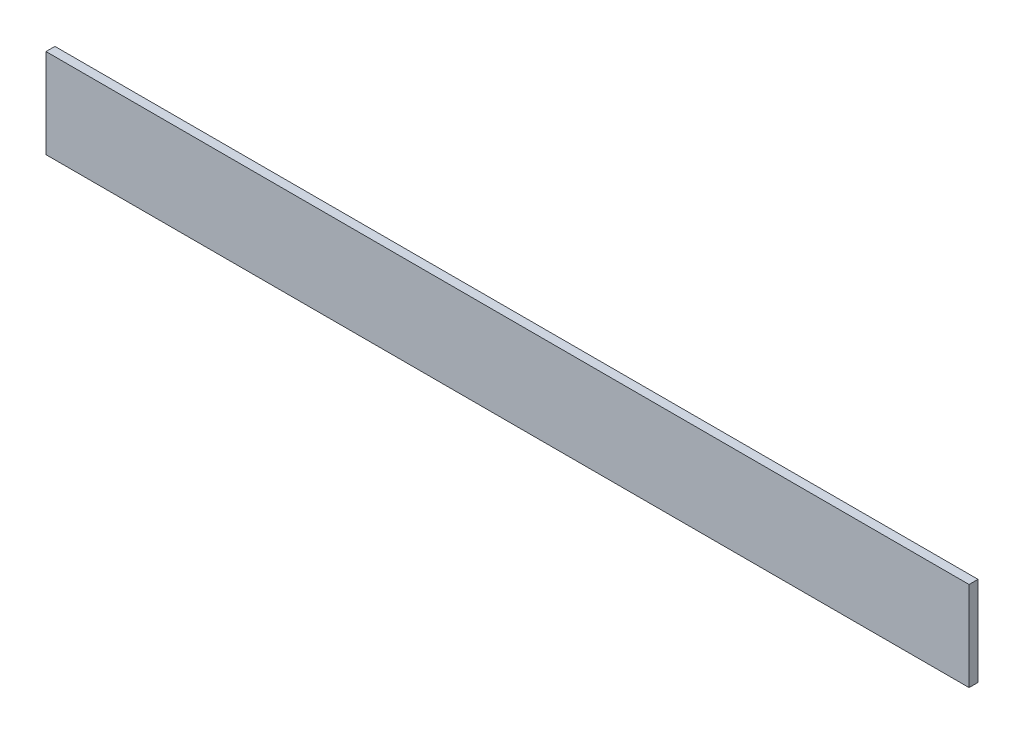
SolidWorks part; units mm, degrees
ref_plane "Спереди" through (0, 0, 0) normal (0, 0, 1) x (1, 0, 0)
ref_plane "Сверху" through (0, 0, 0) normal (0, 1, 0) x (1, 0, 0)
ref_plane "Справа" through (0, 0, 0) normal (1, 0, 0) x (0, 0, -1)
sketch "Эскиз1" plane through (0, 0, 0) normal (1, 0, 0) x (0, 0, -1)
  line L0 (0, 0) -> (30, 0)
  line L1 (0, 0) -> (0, 30)
extrude "Вытянуть-Тонкостенный1" add sketch "Эскиз1" along normal blind 310 thin thin type one direction wall 3
sketch "Эскиз2" plane through (0, 0, 0) normal (0, -1, 0) x (1, 0, 0)
  line L1 (283, -30) -> (310, -30)
  line L2 (283, -30) -> (283, -3)
  line L3 (283, -3) -> (310, -3)
  line L4 (310, -30) -> (310, -3)
extrude "Вырез-Вытянуть1" cut sketch "Эскиз2" against normal through all
